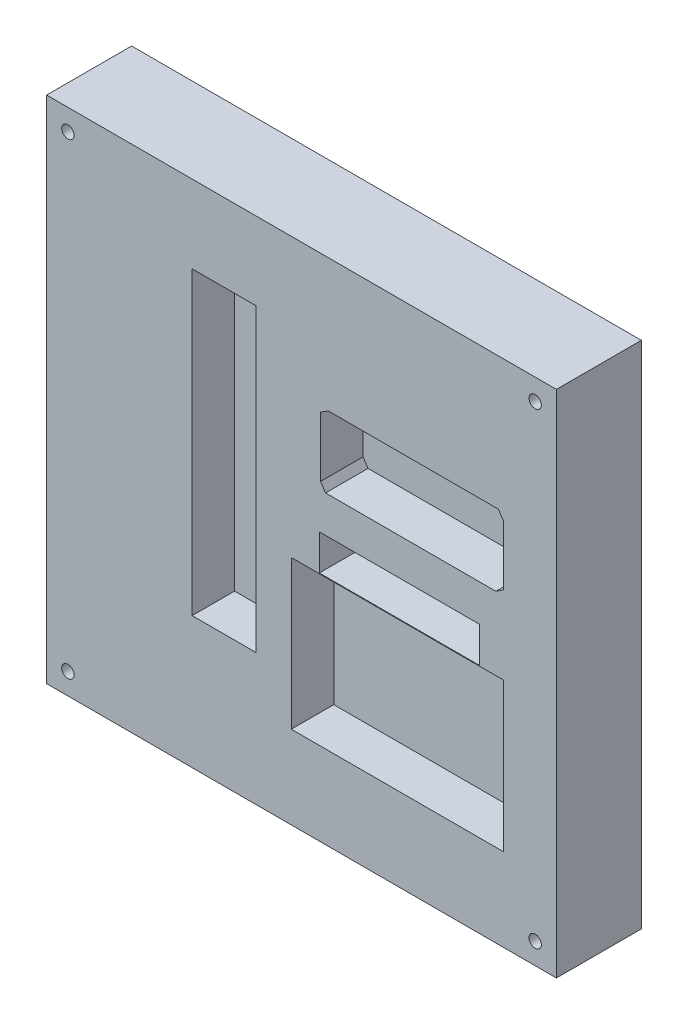
SolidWorks part; units mm, degrees
note: The reader was unsure of these and kept them because the rebuilt part matched: shared geometry of "Sketch1<3>".
ref_plane "Front Plane" through (0, 0, 0) normal (1, 0, 0) x (0, 1, 0)
ref_plane "Top Plane" through (0, 0, 0) normal (0, 0, 1) x (0, 1, 0)
ref_plane "Right Plane" through (0, 0, 0) normal (0, 1, 0) x (-1, 0, 0)
sketch "Sketch1" plane through (0, 0, 0) normal (0, 0, 1) x (0, 1, 0)
  line L0 (0, 0) -> (0, -50)
  line L1 (-50, -50) -> (50, -50)
  line L2 (-50, -50) -> (-50, 50)
  line L3 (-50, 50) -> (50, 50)
  line L4 (50, -50) -> (50, 50)
  line L5 (0, 0) -> (50, 0)
  line L6 (-60, -60) -> (-60, 60)
  line L7 (-60, 60) -> (60, 60)
  line L8 (60, -60) -> (60, 60)
  line L9 (-60, -60) -> (60, -60)
  line L10 (-46, -47.6) -> (-46, -50) construction
  line L11 (-46, -47.6) -> (-46, -44.4) construction
  line L12 (-46, -46) -> (-50, -46) construction
  line L13 (42.5, -0.1) -> (42.5, 3.1) construction
  line L15 (-60, -60) -> (-50, -50) construction
  circle A0 centre (-46, -46) radius 1.45
  circle A1 centre (42.5, 1.5) radius 1.45
  circle A2 centre (-55, -55) radius 1.45
  circle A3 centre (-55, 55) radius 1.45
  circle A4 centre (55, -55) radius 1.45
  circle A5 centre (55, 55) radius 1.45
  point P0 (0, 0)
  dimension "D3" = 2.9
  dimension "D4" = 2.9
  dimension "D5" = 2.9
  dimension "D1" = 100
  dimension "D2" = 10
extrude "Boss-Extrude1" add sketch "Sketch1" along normal blind 3 contours L6 L7 L8 L9
extrude "Boss-Extrude2" add sketch "Sketch1<3>" along normal blind 10 contours A0 | A1 | L8 L7 L6 L9 | L2 L3 L4 L1 | A3 | A5 | A4 | A2
sketch "Sketch1<3>" plane through (0, 0, 0) normal (0, 0, 1) x (0, 1, 0) same geometry as "Sketch1"
sketch "Sketch5" plane through (0, 0, 0) normal (0, 0, 1) x (0, 1, 0)
  line L0 (-27.34, 24.2901) -> (-15.6601, 12.21)
  line L1 (-15.6599, 24.2899) -> (-27.3401, 12.2101)
  line L2 (-37.575, -0.455) -> (-8.515, -0.455)
  line L3 (-29, 25.75) -> (-29, 10.75)
  line L8 (-29, 25.75) -> (-14, 25.75)
  line L9 (-14, 25.75) -> (-14, 10.75)
  line L10 (-29, 10.75) -> (-14, 10.75)
  line L11 (-29, 25.75) -> (-14, 10.75) construction
  line L12 (-23.545, -14.485) -> (-23.545, -0.515)
  line L13 (-23.605, -0.455) -> (-37.575, -0.455)
  line L14 (-37.635, -0.515) -> (-37.635, -14.485)
  line L15 (-37.575, -14.545) -> (-23.605, -14.545)
  line L16 (-14, 25.75) -> (-29, 10.75) construction
  line L17 (-8.515, -0.455) -> (-8.515, -44.725)
  line L18 (-37.635, -0.515) -> (-37.635, -44.665)
  line L19 (-17.1035, -15.545) -> (-37.635, -15.545)
  line L20 (-23.545, -44.665) -> (-23.545, -30.695)
  line L21 (-23.605, -30.635) -> (-37.575, -30.635)
  line L22 (-37.635, -30.695) -> (-37.635, -44.665)
  line L23 (-37.575, -44.725) -> (-23.605, -44.725)
  line L24 (28.75, -6.2417) -> (27.5741, -4.4817)
  line L25 (27.5741, -4.4817) -> (13.4718, -4.4799)
  line L26 (-19.5284, -29.635) -> (-37.635, -29.635)
  line L27 (-37.635, -29.635) -> (-8.455, -15.605)
  line L28 (-37.635, -15.545) -> (-8.455, -29.575)
  line L30 (-40.4826, 2.41) -> (-40.4826, -47.59)
  line L31 (-40.4826, 2.41) -> (-5.4826, 2.41)
  line L32 (-5.4826, 2.41) -> (-5.4826, -47.59)
  line L33 (-40.4826, -47.59) -> (-5.4826, -47.59)
  line L34 (-40.4826, 2.41) -> (-5.4826, -47.59) construction
  line L35 (-5.4826, 2.41) -> (-40.4826, -47.59) construction
  line L36 (26.25, -7) -> (26.2377, -6.9815)
  line L37 (26.2377, -6.9815) -> (14.23, -6.98)
  line L38 (14.23, -6.98) -> (14.2115, -6.9923)
  line L39 (14.2115, -6.9923) -> (14.21, -45)
  line L40 (14.21, -45) -> (14.2223, -45.0185)
  line L41 (14.2223, -45.0185) -> (26.23, -45.02)
  line L42 (26.23, -45.02) -> (26.2485, -45.0077)
  line L46 (13.4718, -4.4799) -> (11.7116, -5.656)
  line L47 (11.7116, -5.656) -> (11.71, -45.7583)
  line L48 (11.71, -45.7583) -> (12.8859, -47.5183)
  line L49 (12.8859, -47.5183) -> (26.9882, -47.5201)
  line L50 (26.9882, -47.5201) -> (28.7484, -46.344)
  line L51 (28.7484, -46.344) -> (28.75, -6.2417)
  line L52 (1.0414, -41.9) -> (19.1073, -41.9019) construction
  line L53 (50, 50) -> (50, -50)
  line L54 (50, 50) -> (-50, 50)
  line L55 (-50, 50) -> (-50, -50)
  line L56 (50, -50) -> (-50, -50)
  line L57 (50, 50) -> (-50, -50) construction
  line L58 (-50, 50) -> (50, -50) construction
  line L59 (-14, 25.75) -> (41.6996, 25.75)
  line L60 (-14, 25.75) -> (-14, 10.75)
  line L61 (-14, 10.75) -> (41.6996, 10.75)
  line L62 (41.6996, 25.75) -> (41.6996, 10.75)
  line L63 (-5.331, -4.1896) -> (3.0598, -4.1896)
  line L64 (-5.331, -4.1896) -> (-5.331, -41.9002)
  line L65 (-5.331, -41.9002) -> (3.0598, -41.9002)
  line L66 (3.0598, -4.1896) -> (3.0598, -41.9002)
  line L67 (-60, 60) -> (-60, -60)
  line L68 (60, -60) -> (-60, -60)
  line L69 (60, 60) -> (60, -60)
  line L70 (60, 60) -> (-60, 60)
  line L71 (-60, -60) -> (-50, -50)
  line L72 (-50, 50) -> (-60, 60)
  line L73 (50, 50) -> (60, 60)
  line L74 (50, -50) -> (60, -60)
  line L92 (-8.455, -14.485) -> (-8.455, -0.515)
  line L93 (-8.515, -0.455) -> (-22.485, -0.455)
  line L94 (-22.545, -0.515) -> (-22.545, -6.127)
  line L95 (-22.545, -6.127) -> (-22.5916, -6.1512)
  line L96 (-22.5916, -6.1512) -> (-22.6571, -6.2146)
  line L97 (-22.6571, -6.2146) -> (-22.7141, -6.3236)
  line L98 (-22.7141, -6.3236) -> (-22.7654, -6.5214)
  line L99 (-22.7654, -6.5214) -> (-22.8039, -6.5984)
  line L100 (-22.8039, -6.5984) -> (-22.8343, -6.6288)
  line L101 (-22.8343, -6.6288) -> (-22.9028, -6.6631)
  line L102 (-22.9028, -6.6631) -> (-22.9626, -6.6631)
  line L103 (-23.0958, -6.5299) -> (-23.0958, -6.3217)
  line L104 (-23.0958, -6.3217) -> (-23.052, -6.1904)
  line L105 (-23.1884, -6.1295) -> (-23.2436, -6.2931)
  line L106 (-23.2436, -6.2931) -> (-23.2444, -6.5623)
  line L107 (-23.2444, -6.5623) -> (-23.1863, -6.6827)
  line L108 (-23.1863, -6.6827) -> (-23.1229, -6.7482)
  line L109 (-22.75, -6.7536) -> (-22.6845, -6.6901)
  line L110 (-22.6845, -6.6901) -> (-22.6275, -6.5812)
  line L111 (-22.6275, -6.5812) -> (-22.5762, -6.3833)
  line L112 (-22.5762, -6.3833) -> (-22.545, -6.3208)
  line L113 (-22.545, -6.3208) -> (-22.545, -7.0834)
  line L114 (-22.545, -7.0834) -> (-23.1882, -7.2366)
  line L115 (-23.2039, -7.3768) -> (-22.7476, -7.5)
  line L116 (-22.7476, -7.5) -> (-23.1901, -7.618)
  line L117 (-23.2021, -7.7586) -> (-22.545, -7.9166)
  line L118 (-22.545, -7.9166) -> (-22.545, -8.4258)
  line L119 (-22.6253, -8.4854) -> (-22.6268, -8.6252)
  line L120 (-22.6268, -8.6252) -> (-22.661, -8.6937)
  line L121 (-22.661, -8.6937) -> (-22.6914, -8.7241)
  line L122 (-23.0312, -8.7241) -> (-23.0616, -8.6937)
  line L123 (-23.0616, -8.3063) -> (-23.0225, -8.2673)
  line L124 (-23.1172, -8.1519) -> (-23.181, -8.2146)
  line L125 (-23.181, -8.2146) -> (-23.2432, -8.3373)
  line L126 (-23.2432, -8.3373) -> (-23.2444, -8.6575)
  line L127 (-23.2444, -8.6575) -> (-23.1863, -8.7779)
  line L128 (-23.1863, -8.7779) -> (-23.1229, -8.8435)
  line L129 (-22.6135, -8.8528) -> (-22.5464, -8.7911)
  line L130 (-22.5464, -8.7911) -> (-22.545, -14.485)
  line L131 (-22.485, -14.545) -> (-8.515, -14.545)
  line L166 (-8.455, -29.575) -> (-8.455, -15.605)
  line L167 (-8.515, -15.545) -> (-22.485, -15.545)
  line L168 (-22.545, -15.605) -> (-22.545, -21.217)
  line L169 (-22.545, -21.217) -> (-22.5916, -21.2412)
  line L170 (-22.5916, -21.2412) -> (-22.6571, -21.3046)
  line L171 (-22.6571, -21.3046) -> (-22.7141, -21.4136)
  line L172 (-22.7141, -21.4136) -> (-22.7654, -21.6114)
  line L173 (-22.7654, -21.6114) -> (-22.8039, -21.6884)
  line L174 (-22.8039, -21.6884) -> (-22.8343, -21.7188)
  line L175 (-22.8343, -21.7188) -> (-22.9028, -21.7531)
  line L176 (-22.9028, -21.7531) -> (-22.9626, -21.7531)
  line L177 (-23.0958, -21.6199) -> (-23.0958, -21.4117)
  line L178 (-23.0958, -21.4117) -> (-23.052, -21.2804)
  line L179 (-23.1884, -21.2195) -> (-23.2436, -21.3831)
  line L180 (-23.2436, -21.3831) -> (-23.2444, -21.6523)
  line L181 (-23.2444, -21.6523) -> (-23.1863, -21.7727)
  line L182 (-23.1863, -21.7727) -> (-23.1229, -21.8382)
  line L183 (-22.75, -21.8436) -> (-22.6845, -21.7801)
  line L184 (-22.6845, -21.7801) -> (-22.6275, -21.6712)
  line L185 (-22.6275, -21.6712) -> (-22.5762, -21.4733)
  line L186 (-22.5762, -21.4733) -> (-22.545, -21.4108)
  line L187 (-22.545, -21.4108) -> (-22.545, -22.1734)
  line L188 (-22.545, -22.1734) -> (-23.1882, -22.3266)
  line L189 (-23.2039, -22.4668) -> (-22.7476, -22.59)
  line L190 (-22.7476, -22.59) -> (-23.1901, -22.708)
  line L191 (-23.2021, -22.8486) -> (-22.545, -23.0066)
  line L192 (-22.545, -23.0066) -> (-22.545, -23.2867)
  line L193 (-22.545, -23.2867) -> (-22.6542, -23.2773)
  line L194 (-22.7132, -23.3872) -> (-22.661, -23.444)
  line L195 (-22.661, -23.7837) -> (-22.6914, -23.8141)
  line L196 (-23.0312, -23.8141) -> (-23.0616, -23.7837)
  line L197 (-23.0616, -23.444) -> (-23.0225, -23.4049)
  line L198 (-23.1172, -23.2895) -> (-23.181, -23.3522)
  line L199 (-23.1863, -23.8679) -> (-23.1229, -23.9335)
  line L200 (-22.6135, -23.9428) -> (-22.5464, -23.8811)
  line L201 (-22.5464, -23.8811) -> (-22.545, -29.575)
  line L202 (-22.485, -29.635) -> (-8.515, -29.635)
  line L228 (-8.455, -44.665) -> (-8.455, -30.695)
  line L229 (-8.515, -30.635) -> (-22.485, -30.635)
  line L230 (-22.545, -30.695) -> (-22.545, -36.307)
  line L231 (-22.545, -36.307) -> (-22.5916, -36.3312)
  line L232 (-22.5916, -36.3312) -> (-22.6571, -36.3946)
  line L233 (-22.6571, -36.3946) -> (-22.7141, -36.5036)
  line L234 (-22.7141, -36.5036) -> (-22.7654, -36.7014)
  line L235 (-22.7654, -36.7014) -> (-22.8039, -36.7784)
  line L236 (-22.8039, -36.7784) -> (-22.8343, -36.8088)
  line L237 (-22.8343, -36.8088) -> (-22.9028, -36.8431)
  line L238 (-22.9028, -36.8431) -> (-22.9626, -36.8431)
  line L239 (-23.0958, -36.7099) -> (-23.0958, -36.5017)
  line L240 (-23.0958, -36.5017) -> (-23.052, -36.3704)
  line L241 (-23.1884, -36.3095) -> (-23.2436, -36.4731)
  line L242 (-23.2436, -36.4731) -> (-23.2444, -36.7423)
  line L243 (-23.2444, -36.7423) -> (-23.1863, -36.8627)
  line L244 (-23.1863, -36.8627) -> (-23.1229, -36.9282)
  line L245 (-22.75, -36.9336) -> (-22.6845, -36.8701)
  line L246 (-22.6845, -36.8701) -> (-22.6275, -36.7612)
  line L247 (-22.6275, -36.7612) -> (-22.5762, -36.5633)
  line L248 (-22.5762, -36.5633) -> (-22.545, -36.5008)
  line L249 (-22.545, -36.5008) -> (-22.545, -37.2634)
  line L250 (-22.545, -37.2634) -> (-23.1882, -37.4166)
  line L251 (-23.2039, -37.5568) -> (-22.7476, -37.68)
  line L252 (-22.7476, -37.68) -> (-23.1901, -37.798)
  line L253 (-23.2021, -37.9386) -> (-22.545, -38.0966)
  line L254 (-22.545, -38.0966) -> (-22.545, -38.819)
  line L255 (-22.545, -38.819) -> (-23.1413, -38.5634)
  line L256 (-23.2132, -38.6942) -> (-22.545, -38.9822)
  line L257 (-22.545, -38.9822) -> (-22.545, -44.665)
  line L258 (-22.485, -44.725) -> (-8.515, -44.725)
  line L259 (26.2485, -45.0077) -> (26.25, -7)
  line L264 (-15.54, 20.2499) -> (-15.54, 24.3499)
  line L265 (-15.6, 24.4099) -> (-27.4, 24.4099)
  line L266 (-27.46, 24.3499) -> (-27.46, 20.2499)
  line L267 (-27.34, 20.2499) -> (-27.34, 24.2901)
  line L268 (-27.34, 24.2901) -> (-15.6599, 24.2899)
  line L269 (-15.6599, 24.2899) -> (-15.66, 20.2499)
  line L276 (-15.54, 12.15) -> (-15.54, 16.25)
  line L277 (-15.66, 16.25) -> (-15.6601, 12.21)
  line L278 (-15.6601, 12.21) -> (-18.0001, 12.21)
  line L279 (-18.0001, 12.09) -> (-15.6, 12.09)
  line L280 (-22.8, 12.09) -> (-20.2, 12.09)
  line L281 (-20.177, 12.2054) -> (-20.2, 12.21)
  line L282 (-20.2, 12.21) -> (-22.8, 12.21)
  line L283 (-27.4001, 12.0901) -> (-25.0001, 12.0901)
  line L284 (-24.9771, 12.2055) -> (-25.0001, 12.2101)
  line L285 (-25.0001, 12.2101) -> (-27.3401, 12.2101)
  line L286 (-27.3401, 12.2101) -> (-27.3401, 16.2501)
  line L287 (-27.4601, 16.2501) -> (-27.4601, 12.1501)
  circle A0 centre (-55, -55) radius 1.45
  circle A1 centre (-55, 55) radius 1.45
  circle A2 centre (55, 55) radius 1.45
  circle A3 centre (55, -55) radius 1.45
  spline S12 degree 2 poles (-23.545, -0.515) (-23.545, -0.4905) (-23.5626, -0.4726) (-23.5798, -0.455) (-23.605, -0.455) knots 0 0 0 0.5 0.5 1 1 1
  spline S13 degree 2 poles (-37.575, -0.455) (-37.5995, -0.455) (-37.6174, -0.4726) (-37.635, -0.4898) (-37.635, -0.515) knots 0 0 0 0.5 0.5 1 1 1
  spline S14 degree 2 poles (-37.635, -14.485) (-37.635, -14.5095) (-37.6174, -14.5274) (-37.6002, -14.545) (-37.575, -14.545) knots 0 0 0 0.5 0.5 1 1 1
  spline S15 degree 2 poles (-23.605, -14.545) (-23.5805, -14.545) (-23.5626, -14.5274) (-23.545, -14.5102) (-23.545, -14.485) knots 0 0 0 0.5 0.5 1 1 1
  spline S20 degree 2 poles (-23.545, -30.695) (-23.545, -30.6705) (-23.5626, -30.6526) (-23.5798, -30.635) (-23.605, -30.635) knots 0 0 0 0.5 0.5 1 1 1
  spline S21 degree 2 poles (-37.575, -30.635) (-37.5995, -30.635) (-37.6174, -30.6526) (-37.635, -30.6698) (-37.635, -30.695) knots 0 0 0 0.5 0.5 1 1 1
  spline S40 degree 2 poles (-8.455, -0.515) (-8.455, -0.4905) (-8.4726, -0.4726) (-8.4898, -0.455) (-8.515, -0.455) knots 0 0 0 0.5 0.5 1 1 1
  spline S41 degree 2 poles (-22.485, -0.455) (-22.5095, -0.455) (-22.5274, -0.4726) (-22.545, -0.4898) (-22.545, -0.515) knots 0 0 0 0.5 0.5 1 1 1
  spline S42 degree 2 poles (-22.9626, -6.6631) (-23.0112, -6.6503) (-23.0472, -6.6145) (-23.0829, -6.5791) (-23.0958, -6.5299) knots 0 0 0 0.5 0.5 1 1 1
  spline S43 degree 2 poles (-23.052, -6.1904) (-23.043, -6.1632) (-23.0546, -6.1365) (-23.0658, -6.1104) (-23.0926, -6.0982) (-23.1185, -6.0864) (-23.1465, -6.0954) (-23.1739, -6.1041) (-23.1884, -6.1295) knots 0 0 0 0.25 0.25 0.5 0.5 0.75 0.75 1 1 1
  spline S44 degree 2 poles (-23.1229, -6.7482) (-23.0431, -6.8168) (-22.9374, -6.8185) (-22.8322, -6.8202) (-22.75, -6.7536) knots 0 0 0 0.5 0.5 1 1 1
  spline S45 degree 2 poles (-23.1882, -7.2366) (-23.211, -7.242) (-23.227, -7.2598) (-23.2425, -7.2771) (-23.2454, -7.3012) (-23.2481, -7.3242) (-23.2366, -7.3456) (-23.2255, -7.3662) (-23.2039, -7.3768) knots 0 0 0 0.25 0.25 0.5 0.5 0.75 0.75 1 1 1
  spline S46 degree 2 poles (-23.1901, -7.618) (-23.2128, -7.624) (-23.2283, -7.6423) (-23.2433, -7.66) (-23.2456, -7.6841) (-23.2477, -7.7072) (-23.2356, -7.7283) (-23.2239, -7.7486) (-23.2021, -7.7586) knots 0 0 0 0.25 0.25 0.5 0.5 0.75 0.75 1 1 1
  spline S47 degree 2 poles (-22.545, -8.4258) (-22.5733, -8.4229) (-22.5968, -8.44) (-22.6198, -8.4568) (-22.6253, -8.4854) knots 0 0 0 0.5 0.5 1 1 1
  spline S48 degree 2 poles (-22.6914, -8.7241) (-22.7683, -8.7755) (-22.8613, -8.7756) (-22.9538, -8.7758) (-23.0312, -8.7241) knots 0 0 0 0.5 0.5 1 1 1
  spline S49 degree 2 poles (-23.0616, -8.6937) (-23.1182, -8.6054) (-23.1184, -8.5) (-23.1185, -8.3951) (-23.0616, -8.3063) knots 0 0 0 0.5 0.5 1 1 1
  spline S50 degree 2 poles (-23.0225, -8.2673) (-23.0023, -8.2471) (-23.0007, -8.218) (-22.9991, -8.1896) (-23.0176, -8.1667) (-23.0354, -8.1446) (-23.0646, -8.1401) (-23.0929, -8.1357) (-23.1172, -8.1519) knots 0 0 0 0.25 0.25 0.5 0.5 0.75 0.75 1 1 1
  spline S51 degree 2 poles (-23.1229, -8.8435) (-23.0095, -8.9244) (-22.8696, -8.9272) (-22.7303, -8.9299) (-22.6135, -8.8528) knots 0 0 0 0.5 0.5 1 1 1
  spline S52 degree 2 poles (-22.545, -14.485) (-22.545, -14.5095) (-22.5274, -14.5274) (-22.5102, -14.545) (-22.485, -14.545) knots 0 0 0 0.5 0.5 1 1 1
  spline S53 degree 2 poles (-8.515, -14.545) (-8.4905, -14.545) (-8.4726, -14.5274) (-8.455, -14.5102) (-8.455, -14.485) knots 0 0 0 0.5 0.5 1 1 1
  spline S72 degree 2 poles (-8.455, -15.605) (-8.455, -15.5805) (-8.4726, -15.5626) (-8.4898, -15.545) (-8.515, -15.545) knots 0 0 0 0.5 0.5 1 1 1
  spline S73 degree 2 poles (-22.485, -15.545) (-22.5095, -15.545) (-22.5274, -15.5626) (-22.545, -15.5798) (-22.545, -15.605) knots 0 0 0 0.5 0.5 1 1 1
  spline S74 degree 2 poles (-22.9626, -21.7531) (-23.0112, -21.7403) (-23.0472, -21.7045) (-23.0829, -21.6691) (-23.0958, -21.6199) knots 0 0 0 0.5 0.5 1 1 1
  spline S75 degree 2 poles (-23.052, -21.2804) (-23.043, -21.2532) (-23.0546, -21.2265) (-23.0658, -21.2004) (-23.0926, -21.1882) (-23.1185, -21.1764) (-23.1465, -21.1854) (-23.1739, -21.1941) (-23.1884, -21.2195) knots 0 0 0 0.25 0.25 0.5 0.5 0.75 0.75 1 1 1
  spline S76 degree 2 poles (-23.1229, -21.8382) (-23.0431, -21.9068) (-22.9374, -21.9085) (-22.8322, -21.9102) (-22.75, -21.8436) knots 0 0 0 0.5 0.5 1 1 1
  spline S77 degree 2 poles (-23.1882, -22.3266) (-23.211, -22.332) (-23.227, -22.3498) (-23.2425, -22.3671) (-23.2454, -22.3912) (-23.2481, -22.4142) (-23.2366, -22.4356) (-23.2255, -22.4562) (-23.2039, -22.4668) knots 0 0 0 0.25 0.25 0.5 0.5 0.75 0.75 1 1 1
  spline S78 degree 2 poles (-23.1901, -22.708) (-23.2128, -22.714) (-23.2283, -22.7323) (-23.2433, -22.75) (-23.2456, -22.7741) (-23.2477, -22.7972) (-23.2356, -22.8183) (-23.2239, -22.8386) (-23.2021, -22.8486) knots 0 0 0 0.25 0.25 0.5 0.5 0.75 0.75 1 1 1
  spline S79 degree 2 poles (-22.6542, -23.2773) (-22.6938, -23.2811) (-22.7131, -23.3165) (-22.7322, -23.3515) (-22.7132, -23.3872) knots 0 0 0 0.5 0.5 1 1 1
  spline S80 degree 2 poles (-22.661, -23.444) (-22.6096, -23.5208) (-22.6095, -23.6138) (-22.6093, -23.7063) (-22.661, -23.7837) knots 0 0 0 0.5 0.5 1 1 1
  spline S81 degree 2 poles (-22.6914, -23.8141) (-22.7683, -23.8655) (-22.8613, -23.8656) (-22.9538, -23.8658) (-23.0312, -23.8141) knots 0 0 0 0.5 0.5 1 1 1
  spline S82 degree 2 poles (-23.0616, -23.7837) (-23.1129, -23.7068) (-23.1131, -23.6138) (-23.1133, -23.5213) (-23.0616, -23.444) knots 0 0 0 0.5 0.5 1 1 1
  spline S83 degree 2 poles (-23.0225, -23.4049) (-23.0023, -23.3847) (-23.0007, -23.3556) (-22.9991, -23.3273) (-23.0176, -23.3043) (-23.0354, -23.2823) (-23.0646, -23.2777) (-23.0929, -23.2733) (-23.1172, -23.2895) knots 0 0 0 0.25 0.25 0.5 0.5 0.75 0.75 1 1 1
  spline S84 degree 2 poles (-23.181, -23.3522) (-23.2629, -23.4674) (-23.2646, -23.6092) (-23.2662, -23.7506) (-23.1863, -23.8679) knots 0 0 0 0.5 0.5 1 1 1
  spline S85 degree 2 poles (-23.1229, -23.9335) (-23.0095, -24.0144) (-22.8696, -24.0172) (-22.7303, -24.0199) (-22.6135, -23.9428) knots 0 0 0 0.5 0.5 1 1 1
  spline S86 degree 2 poles (-22.545, -29.575) (-22.545, -29.5995) (-22.5274, -29.6174) (-22.5102, -29.635) (-22.485, -29.635) knots 0 0 0 0.5 0.5 1 1 1
  spline S87 degree 2 poles (-8.515, -29.635) (-8.4905, -29.635) (-8.4726, -29.6174) (-8.455, -29.6002) (-8.455, -29.575) knots 0 0 0 0.5 0.5 1 1 1
  spline S92 degree 2 poles (-8.455, -30.695) (-8.455, -30.6705) (-8.4726, -30.6526) (-8.4898, -30.635) (-8.515, -30.635) knots 0 0 0 0.5 0.5 1 1 1
  spline S93 degree 2 poles (-22.485, -30.635) (-22.5095, -30.635) (-22.5274, -30.6526) (-22.545, -30.6698) (-22.545, -30.695) knots 0 0 0 0.5 0.5 1 1 1
  spline S94 degree 2 poles (-22.9626, -36.8431) (-23.0112, -36.8303) (-23.0472, -36.7945) (-23.0829, -36.7591) (-23.0958, -36.7099) knots 0 0 0 0.5 0.5 1 1 1
  spline S95 degree 2 poles (-23.052, -36.3704) (-23.043, -36.3432) (-23.0546, -36.3165) (-23.0658, -36.2904) (-23.0926, -36.2782) (-23.1185, -36.2664) (-23.1465, -36.2754) (-23.1739, -36.2841) (-23.1884, -36.3095) knots 0 0 0 0.25 0.25 0.5 0.5 0.75 0.75 1 1 1
  spline S96 degree 2 poles (-23.1229, -36.9282) (-23.0431, -36.9968) (-22.9374, -36.9985) (-22.8322, -37.0002) (-22.75, -36.9336) knots 0 0 0 0.5 0.5 1 1 1
  spline S97 degree 2 poles (-23.1882, -37.4166) (-23.211, -37.422) (-23.227, -37.4398) (-23.2425, -37.4571) (-23.2454, -37.4812) (-23.2481, -37.5042) (-23.2366, -37.5256) (-23.2255, -37.5462) (-23.2039, -37.5568) knots 0 0 0 0.25 0.25 0.5 0.5 0.75 0.75 1 1 1
  spline S98 degree 2 poles (-23.1901, -37.798) (-23.2128, -37.804) (-23.2283, -37.8223) (-23.2433, -37.84) (-23.2456, -37.8641) (-23.2477, -37.8872) (-23.2356, -37.9083) (-23.2239, -37.9286) (-23.2021, -37.9386) knots 0 0 0 0.25 0.25 0.5 0.5 0.75 0.75 1 1 1
  spline S99 degree 2 poles (-23.1413, -38.5634) (-23.1676, -38.5522) (-23.1952, -38.5615) (-23.2221, -38.5705) (-23.2365, -38.5962) (-23.2504, -38.621) (-23.2438, -38.6497) (-23.2374, -38.6777) (-23.2132, -38.6942) knots 0 0 0 0.25 0.25 0.5 0.5 0.75 0.75 1 1 1
  spline S100 degree 2 poles (-22.545, -44.665) (-22.545, -44.6895) (-22.5274, -44.7074) (-22.5102, -44.725) (-22.485, -44.725) knots 0 0 0 0.5 0.5 1 1 1
  spline S101 degree 2 poles (-8.515, -44.725) (-8.4905, -44.725) (-8.4726, -44.7074) (-8.455, -44.6902) (-8.455, -44.665) knots 0 0 0 0.5 0.5 1 1 1
  spline S102 degree 2 poles (-37.635, -44.665) (-37.635, -44.6895) (-37.6174, -44.7074) (-37.6002, -44.725) (-37.575, -44.725) knots 0 0 0 0.5 0.5 1 1 1
  spline S103 degree 2 poles (-23.605, -44.725) (-23.5805, -44.725) (-23.5626, -44.7074) (-23.545, -44.6902) (-23.545, -44.665) knots 0 0 0 0.5 0.5 1 1 1
  spline S108 degree 2 poles (-15.54, 24.3499) (-15.54, 24.3744) (-15.5575, 24.3923) (-15.5748, 24.4099) (-15.6, 24.4099) knots 0 0 0 0.5 0.5 1 1 1
  spline S109 degree 2 poles (-27.4, 24.4099) (-27.4245, 24.4099) (-27.4424, 24.3923) (-27.46, 24.3751) (-27.46, 24.3499) knots 0 0 0 0.5 0.5 1 1 1
  spline S110 degree 2 poles (-27.46, 20.2499) (-27.46, 20.2254) (-27.4424, 20.2075) (-27.4254, 20.1901) (-27.4, 20.1899) (-27.3757, 20.1897) (-27.3575, 20.2075) (-27.34, 20.2247) (-27.34, 20.2499) knots 0 0 0 0.25 0.25 0.5 0.5 0.75 0.75 1 1 1
  spline S111 degree 2 poles (-15.66, 20.2499) (-15.66, 20.2254) (-15.6424, 20.2075) (-15.6254, 20.1901) (-15.6, 20.1899) (-15.5757, 20.1897) (-15.5575, 20.2075) (-15.54, 20.2247) (-15.54, 20.2499) knots 0 0 0 0.25 0.25 0.5 0.5 0.75 0.75 1 1 1
  spline S116 degree 2 poles (-15.54, 16.25) (-15.54, 16.2745) (-15.5576, 16.2924) (-15.5746, 16.3098) (-15.6, 16.31) (-15.6243, 16.3102) (-15.6425, 16.2924) (-15.66, 16.2752) (-15.66, 16.25) knots 0 0 0 0.25 0.25 0.5 0.5 0.75 0.75 1 1 1
  spline S117 degree 2 poles (-18.0001, 12.21) (-18.0246, 12.21) (-18.0425, 12.1924) (-18.0598, 12.1754) (-18.0601, 12.15) (-18.0603, 12.1257) (-18.0425, 12.1076) (-18.0252, 12.09) (-18.0001, 12.09) knots 0 0 0 0.25 0.25 0.5 0.5 0.75 0.75 1 1 1
  spline S118 degree 2 poles (-15.6, 12.09) (-15.5755, 12.09) (-15.5576, 12.1076) (-15.54, 12.1248) (-15.54, 12.15) knots 0 0 0 0.5 0.5 1 1 1
  spline S119 degree 2 poles (-20.2, 12.09) (-20.1788, 12.09) (-20.1619, 12.1036) (-20.1456, 12.1167) (-20.1412, 12.1383) (-20.1369, 12.1588) (-20.1471, 12.1783) (-20.1569, 12.1971) (-20.177, 12.2054) knots 0 0 0 0.25 0.25 0.5 0.5 0.75 0.75 1 1 1
  spline S120 degree 2 poles (-22.8, 12.21) (-22.8245, 12.21) (-22.8424, 12.1924) (-22.8598, 12.1754) (-22.86, 12.15) (-22.8602, 12.1257) (-22.8424, 12.1076) (-22.8252, 12.09) (-22.8, 12.09) knots 0 0 0 0.25 0.25 0.5 0.5 0.75 0.75 1 1 1
  spline S121 degree 2 poles (-25.0001, 12.0901) (-24.979, 12.0901) (-24.962, 12.1037) (-24.9458, 12.1168) (-24.9413, 12.1384) (-24.937, 12.1589) (-24.9472, 12.1784) (-24.957, 12.1972) (-24.9771, 12.2055) knots 0 0 0 0.25 0.25 0.5 0.5 0.75 0.75 1 1 1
  spline S122 degree 2 poles (-27.3401, 16.2501) (-27.3401, 16.2746) (-27.3577, 16.2925) (-27.3747, 16.3099) (-27.4001, 16.3101) (-27.4244, 16.3103) (-27.4425, 16.2925) (-27.4601, 16.2753) (-27.4601, 16.2501) knots 0 0 0 0.25 0.25 0.5 0.5 0.75 0.75 1 1 1
  spline S123 degree 2 poles (-27.4601, 12.1501) (-27.4601, 12.1256) (-27.4425, 12.1077) (-27.4253, 12.0901) (-27.4001, 12.0901) knots 0 0 0 0.5 0.5 1 1 1
  point P196 (-21.5, 18.25)
  point P211 (-22.9826, -22.59)
  point P224 (0, 0)
  dimension "D5" = 2.9
  dimension "D6" = 2.9
  dimension "D7" = 2.9
  dimension "D8" = 2.9
  dimension "D1" = 15
  dimension "D2" = 35
  dimension "D3" = 50
  dimension "D4" = 10
extrude "Boss-Extrude3" add sketch "Sketch5" along normal blind 10 from offset 10 contours L56 L53 L54 L55 L51 L50 L49 L48 L47 L46 L25 L24 L33 L30 L31 L32 L59 L62 L61 L10 L3 L8 L63 L66 L65 L64 | L69 L70 L67 L68 L53 L56 L55 L54 | A1 L72 L67 L71 A0 L55 | A3 L74 L56 L71 A0 L68 | A2 L73 L70 L72 A1 L54
